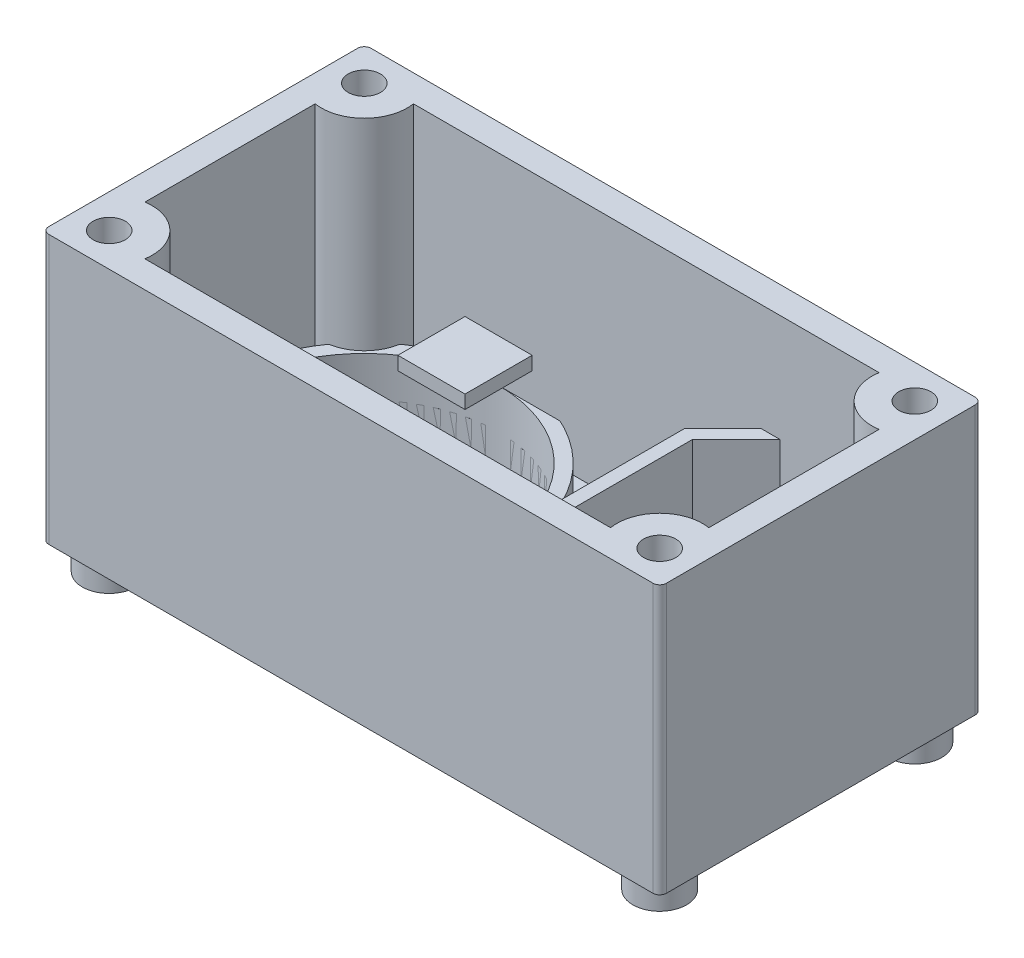
SolidWorks part; units mm, degrees
ref_plane "Front Plane" through (0, 0, 0) normal (0, 0, 1) x (1, 0, 0)
ref_plane "Top Plane" through (0, 0, 0) normal (0, 1, 0) x (1, 0, 0)
ref_plane "Right Plane" through (0, 0, 0) normal (1, 0, 0) x (0, 0, -1)
sketch "Sketch1" plane through (0, 0, 0) normal (0, 1, 0) x (1, 0, 0)
  line L0 (0, 6) -> (0, 0) construction
  line L1 (11.5, -6) -> (-11.5, -6)
  line L2 (11.5, -6) -> (11.5, 6)
  line L3 (11.5, 6) -> (-11.5, 6)
  line L4 (-11.5, -6) -> (-11.5, 6)
  line L5 (11.5, -6) -> (-11.5, 6) construction
  line L6 (11.5, 6) -> (-11.5, -6) construction
  circle A0 centre (-10.25, -4.75) radius 0.6
  circle A1 centre (-10.25, 4.75) radius 0.6
  circle A2 centre (10.25, -4.75) radius 0.6
  circle A3 centre (10.25, 4.75) radius 0.6
  point P0 (0, 0)
  dimension "D5" = 1.2
  dimension "D1" = 12
  dimension "D2" = 23
  dimension "D3" = 1.25
  dimension "D4" = 1.25
  dimension "D6" = 1.25
extrude "Boss-Extrude1" add sketch "Sketch1" along normal blind 10
shell "Shell2" thickness 1 removed face at (10.25, 10, 4.15)
extrude "Extrude-Thin1" add sketch "Sketch1<3>" along normal blind 1 from offset 1 thin contours A0 | A3 | A2 | A1 body kept at (11.5, 10, 6) offset against normal yes thin type one direction wall 0.4
sketch "Sketch1<3>" plane through (0, 0, 0) normal (0, 1, 0) x (1, 0, 0) same geometry as "Sketch1"
sketch "Sketch3" plane through (0, 0, 0) normal (0, -1, 0) x (1, 0, 0)
  line L0 (11.5, 6) -> (11.5, -6) construction
  line L1 (-11.5, 6) -> (-11.5, -6) construction
  circle A0 centre (-5.5, 0) radius 5
  circle A1 centre (6.75, 0) radius 1.55
  circle A3 centre (0.63, 0) radius 0.75
  dimension "D1" = 3.1
  dimension "D3" = 10
  dimension "D5" = 6.13
  dimension "D6" = 1.5
  dimension "D2" = 4.75
  dimension "D4" = 6
extrude "Cut-Extrude1" cut sketch "Sketch3" against normal up to next contours A0 | A1
extrude "Extrude-Thin2" add sketch "Sketch3<3>" along normal blind 0.4 thin contours A3 thin type one direction reverse wall 0.2
sketch "Sketch3<3>" plane through (0, 0, 0) normal (0, -1, 0) x (1, 0, 0) same geometry as "Sketch3"
sketch "Sketch4" plane through (0, 1, 0) normal (0, 1, 0) x (1, 0, 0)
  circle A0 centre (0.63, 0) radius 0.55 construction
  circle A1 centre (0.63, 0) radius 0.55
extrude "Cut-Extrude2" cut sketch "Sketch4" along normal blind 0.35 from offset 1 offset against normal yes
sketch "Sketch5" plane through (0, 1, 0) normal (0, 1, 0) x (1, 0, 0)
  line L0 (4.975, 5) -> (3.35, 3.375)
  line L1 (8.6697, 5) -> (-5.5, 5) construction
  line L2 (3.35, 3.375) -> (3.35, -3.375)
  line L3 (3.35, -3.375) -> (4.975, -5)
  line L4 (-5.5, -5) -> (8.6697, -5) construction
  line L5 (10.5, -3.1697) -> (10.5, 3.1697) construction
  dimension "D1" = 7.15
  dimension "D2" = 135
  dimension "D3" = 135
  dimension "D4" = 6.75
extrude "Extrude-Thin3" add sketch "Sketch5" along normal blind 5 thin thin type one direction wall 0.5
extrude "Extrude-Thin4" add sketch "Sketch3<4>" against normal blind 2.5 separate body thin contours A0 thin type one direction wall 0.5
sketch "Sketch3<4>" plane through (0, 0, 0) normal (0, -1, 0) x (1, 0, 0) same geometry as "Sketch3"
sketch "Sketch7" plane through (0, 0, 0) normal (0, -1, 0) x (1, 0, 0)
  line L0 (-8.6697, 5) -> (-5.5, 5) construction
  line L1 (-6.75, 5) -> (-4.25, 5)
  line L2 (-6.75, 5) -> (-6.75, 2.5)
  line L3 (-6.75, 2.5) -> (-4.25, 2.5)
  line L4 (-4.25, 5) -> (-4.25, 2.5)
  line L5 (-5.5, 0) -> (-2.5596, 0) construction
  line L6 (-6.75, -2.5) -> (-4.25, -2.5)
  line L7 (-4.25, -5) -> (-4.25, -2.5)
  line L8 (-6.75, -5) -> (-4.25, -5)
  line L9 (-6.75, -5) -> (-6.75, -2.5)
  point P6 (-5.5, 2.5)
  dimension "D1" = 2.5
extrude "Boss-Extrude4" add sketch "Sketch7" against normal blind 0.5 from offset 3.6 offset against normal yes
fillet "Fillet2" radius 0.25 4 edges at (11.5, 5, 6) (-11.5, 5, 6) (11.5, 5, -6) (-11.5, 5, -6)
